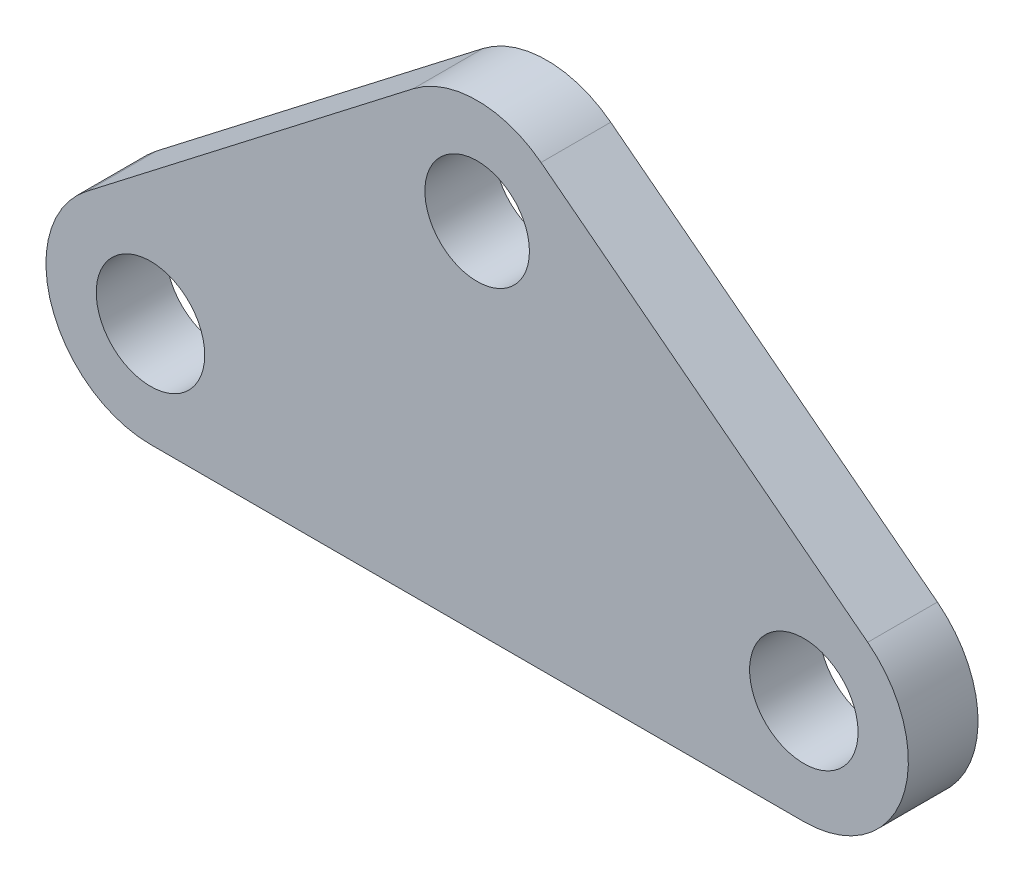
SolidWorks part; units mm, degrees
material "Pine"
ref_plane "Front Plane" through (0, 0, 0) normal (0, 0, 1) x (1, 0, 0)
ref_plane "Top Plane" through (0, 0, 0) normal (0, 1, 0) x (1, 0, 0)
ref_plane "Right Plane" through (0, 0, 0) normal (1, 0, 0) x (0, 0, -1)
sketch "Sketch1" plane through (0, 0, 0) normal (0, 0, 1) x (1, 0, 0)
  line L0 (0, 27.2364) -> (0, -32.7408) construction
  line L1 (25, -27.3) -> (-25, -27.3)
  line L2 (-29.8887, -12.9675) -> (-4.8887, 6.3325)
  line L3 (29.8887, -12.9675) -> (4.8887, 6.3325)
  line L4 (-25, -11.3) -> (25, -11.3)
  circle A0 centre (0, 0) radius 4
  circle A1 centre (0, 0) radius 11 construction
  circle A2 centre (-25, -19.3) radius 4.15
  arc A3 (-25, -27.3) -> (-29.8887, -12.9675) centre (-25, -19.3) cw
  arc A4 (-4.8887, 6.3325) -> (4.8887, 6.3325) centre (0, 0) cw
  arc A5 (25, -27.3) -> (29.8887, -12.9675) centre (25, -19.3) ccw
  circle A6 centre (25, -19.3) radius 4.15
  arc A7 (-25, -11.3) -> (-29.8887, -12.9675) centre (-25, -19.3) ccw
  arc A8 (25, -11.3) -> (29.8887, -12.9675) centre (25, -19.3) cw
  point P8 (0, 11)
  point P15 (0, -27.3)
  point P21 (0, -11.3)
  dimension "D1" = 8
  dimension "D2" = 22
  dimension "D3" = 8.3
  dimension "D6" = 8
  dimension "D7" = 8
  dimension "D4" = 25
  dimension "D5" = 30.3
extrude "Boss-Extrude2" add sketch "Sketch1" against normal blind 5.333 contours L4 A8 L3 A4 L2 A7 A0 | A8 L4 A7 A3 L1 A5 A2 A6 region at (0, -19.3, 0) region at (0, -4.7483, 0)
equation "\"rod_diameter\"= 8"
equation "\"rod_hole_thickness\"= 4"
equation "\"rod_radius\"= \"rod_diameter\" / 2"
equation "\"platter_diameter\"= 320"
equation "\"platter_radius\"= \"platter_diameter\" / 2"
equation "\"extruder_mount_hole_spacing\"= 75"
equation "\"arm_rod_spacing\"= 40"
equation "\"motor_level_rod_spacing\"= 15"
equation "\"linear_bearing_diameter\"= 15"
equation "\"z_rod_spacing\"= 75"
equation "\"platter_rod_spacing\"= 50"
equation "\"rod_nut_thickness\"= 6.5"
equation "\"rod_nut_inscribed_diameter\"= 13"
equation "\"z_height\"= 400"
equation "\"D1@Sketch1\"=\"rod_diameter\""
equation "\"D3@Sketch1\"=\"rod_diameter\"+\"printed_hole_tolerance\""
equation "\"D4@Sketch1\"=\"platter_rod_spacing\"/2"
equation "\"D6@Sketch1\"=\"rod_radius\"+\"rod_hole_thickness\""
equation "\"D7@Sketch1\"=\"rod_radius\"+\"rod_hole_thickness\""
equation "\"top_frame_spacing\"= 100"
equation "\"z_drive_rod_offset\"= 12"
equation "\"gear_pitch\"=2"
equation "\"r_gear_teeth\"= 450"
equation "\"theta_gear_teeth\"= 385"
equation "\"sheet_thickness\"=5.333"
equation "\"sheet_tab_hole_thickness\"= \"sheet_thickness\""
equation "\"sheet_tab_width\"= \"sheet_thickness\"*2"
equation "\"sheet_double_tab_width\"= 35"
equation "\"sheet_bolt_diameter\"= 3"
equation "\"sheet_bolt_length\"= 16"
equation "\"sheet_nut_diameter\"= 5.5"
equation "\"sheet_nut_thickness\"= 2.5"
equation "\"sheet_nut_depth\"= 10"
equation "\"bearing_outside_diameter\"= 22"
equation "\"bearing_thickness\"= 7"
equation "\"corner_part_thickness\"= \"sheet_thickness\" + \"bearing_thickness\""
equation "\"setscrew_nut_diameter\"= 6"
equation "\"setscrew_nut_thickness\"= 3"
equation "\"setscrew_bolt_diameter\"= 3"
equation "\"motor_shaft_diameter\"= 5.7"
equation "\"printed_hole_tolerance\"= 0.3"
equation "\"D1@Boss-Extrude2\"= \"sheet_thickness\""
